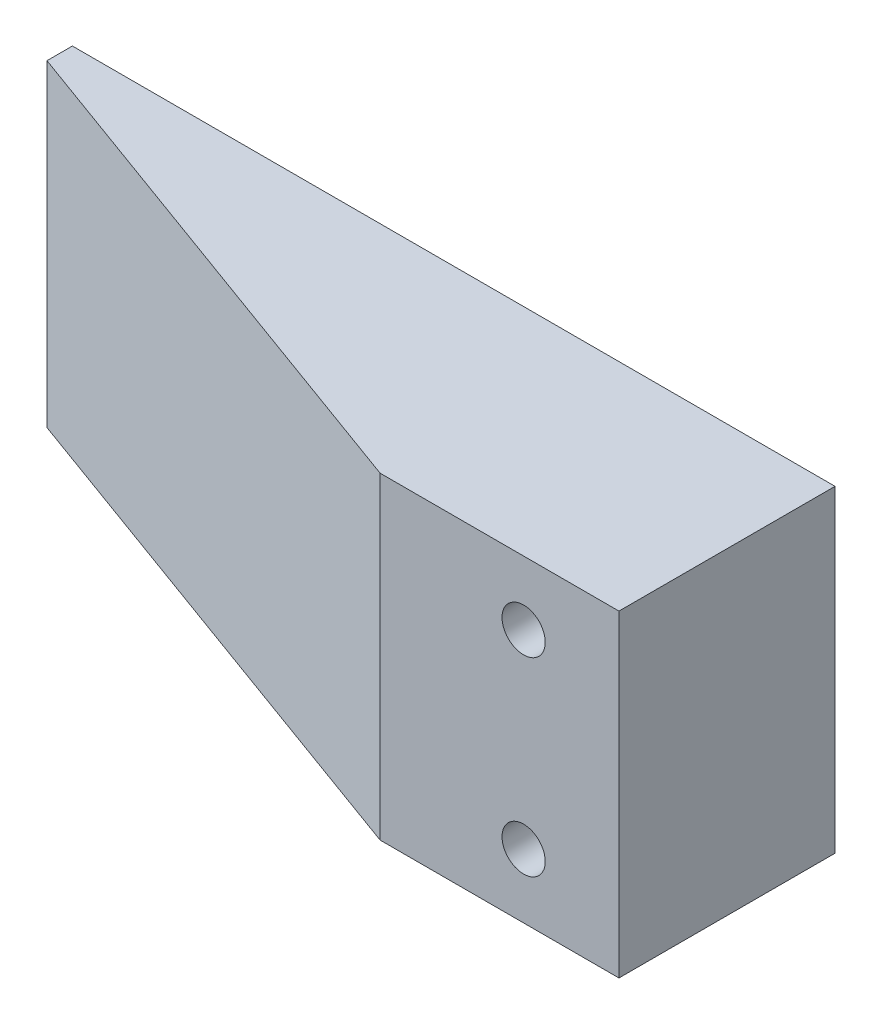
SolidWorks part; units mm, degrees
ref_plane "Front Plane" through (0, 0, 0) normal (0, 0, 1) x (1, 0, 0)
ref_plane "Top Plane" through (0, 0, 0) normal (0, 1, 0) x (1, 0, 0)
ref_plane "Right Plane" through (0, 0, 0) normal (1, 0, 0) x (0, 0, -1)
other "Configuration Table"
sketch "Sketch2" plane through (0, 0, 0) normal (0, 0, 1) x (1, 0, 0)
  line L0 (0, 12.5) -> (0, -12.5) construction
  line L1 (-7.5, 12.5) -> (7.5, 12.5)
  line L2 (-7.5, 12.5) -> (-7.5, -12.5) construction
  line L3 (-7.5, -12.5) -> (7.5, -12.5)
  line L4 (7.5, 12.5) -> (7.5, -12.5)
  line L5 (-7.5, 12.5) -> (7.5, -12.5) construction
  line L6 (-7.5, -12.5) -> (7.5, 12.5) construction
  line L8 (-7.5, 12.5) -> (-52.5, 12.5)
  line L9 (-7.5, 12.5) -> (-7.5, -12.5) construction
  line L10 (-7.5, -12.5) -> (-52.5, -12.5)
  line L11 (-52.5, 12.5) -> (-52.5, -12.5)
  circle A0 centre (0, 7.4667) radius 1.7
  circle A1 centre (0, -7.4667) radius 1.7
  point P0 (0, 0)
  dimension "D1" = 3.4
  dimension "D2" = 3.3333
  dimension "D3" = 3.3333
  dimension "D4" = 25
  dimension "D5" = 15
  dimension "D6" = 45
extrude "Boss-Extrude1" add sketch "Sketch2" along normal blind 8.5 and the other way blind 8.5
chamfer "Chamfer1" distance 15 angle 70 1 edges at (-52.5, 0, 8.5) first distance on face at (-52.5, 0, 0)
